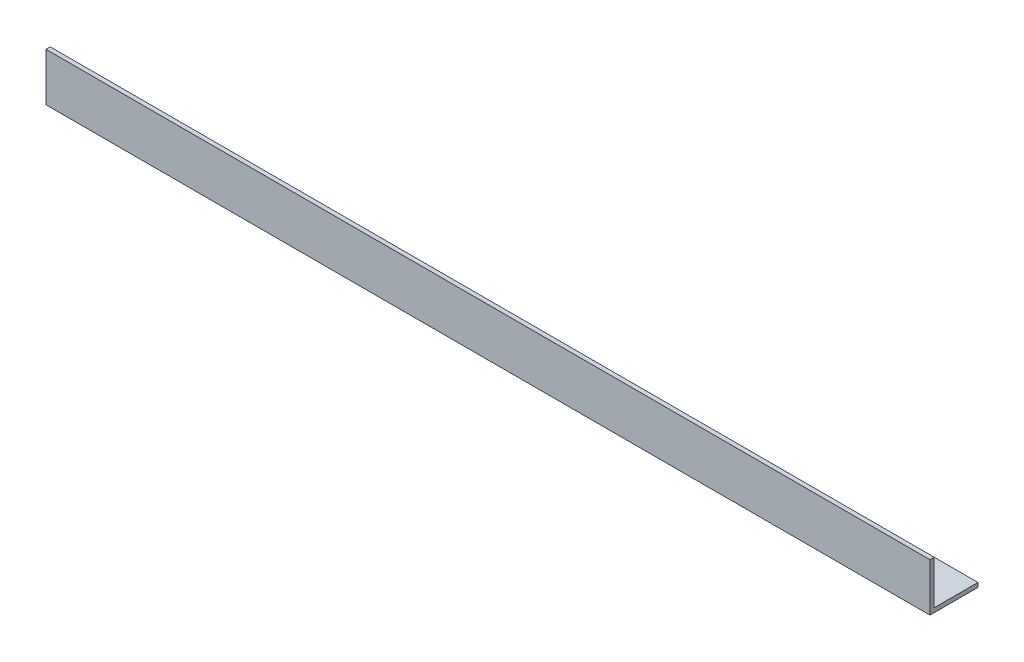
SolidWorks part; units mm, degrees
ref_plane "Спереди" through (0, 0, 0) normal (0, 0, 1) x (1, 0, 0)
ref_plane "Сверху" through (0, 0, 0) normal (0, 1, 0) x (1, 0, 0)
ref_plane "Справа" through (0, 0, 0) normal (1, 0, 0) x (0, 0, -1)
sketch "Эскиз1" plane through (0, 0, 0) normal (1, 0, 0) x (0, 0, -1)
  line L0 (0, 33.7) -> (0, 0)
  line L1 (0, 0) -> (33.7, 0)
extrude "Вытянуть-Тонкостенный1" add sketch "Эскиз1" along normal blind 620 thin thin type one direction reverse wall 3
